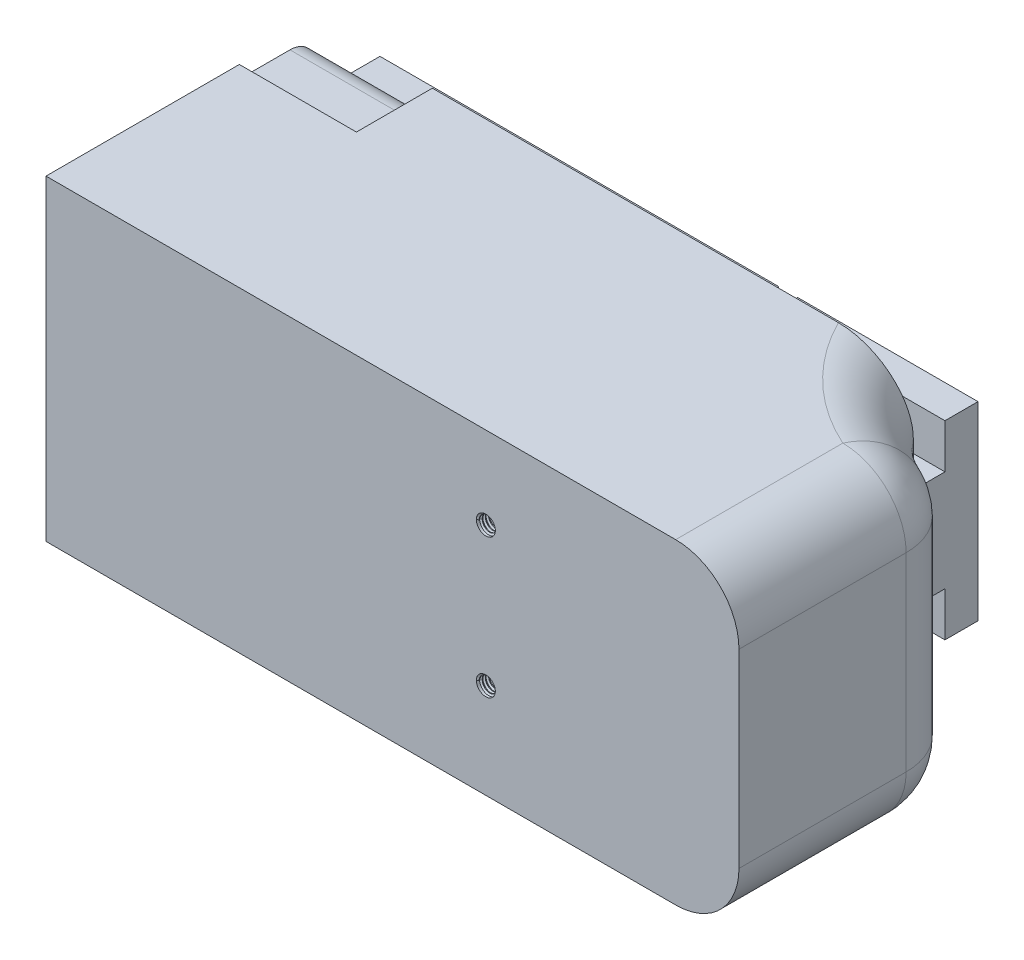
SolidWorks part; units mm, degrees
ref_plane "Front Plane" through (0, 0, 0) normal (0, 0, 1) x (1, 0, 0)
ref_plane "Top Plane" through (0, 0, 0) normal (0, 1, 0) x (1, 0, 0)
ref_plane "Right Plane" through (0, 0, 0) normal (1, 0, 0) x (0, 0, -1)
sketch "Sketch1" plane through (0, 0, 0) normal (0, 0, 1) x (1, 0, 0)
  line L0 (0, 0) -> (0, 50)
  line L1 (0, 50) -> (109.5, 50)
  line L2 (109.5, 50) -> (109.5, 0)
  line L3 (109.5, 0) -> (0, 0)
  dimension "D1" = 109.5
  dimension "D2" = 50
extrude "Boss-Extrude1" add sketch "Sketch1" along normal blind 52.55
sketch "Sketch2" plane through (0, 0, 0) normal (0, -1, 0) x (1, 0, 0)
  line L0 (0, 10) -> (109.5, 10)
  line L1 (0, 52.55) -> (0, 0) construction
  line L2 (109.5, 52.55) -> (109.5, 0) construction
  line L3 (0, 52.55) -> (109.5, 52.55) construction
  line L4 (0, 10) -> (0, 0)
  line L5 (0, 0) -> (109.5, 0)
  line L6 (109.5, 0) -> (109.5, 10)
  dimension "D1" = 42.55
extrude "Cut-Extrude1" cut sketch "Sketch2" against normal blind 10
sketch "Sketch3" plane through (0, 0, 0) normal (0, -1, 0) x (1, 0, 0)
  line L0 (0, 22) -> (18.5, 22)
  line L1 (0, 52.55) -> (0, 10) construction
  line L2 (18.5, 22) -> (18.5, 10)
  line L3 (109.5, 10) -> (0, 10) construction
  line L4 (0, 22) -> (0, 10)
  line L5 (0, 10) -> (18.5, 10)
  dimension "D1" = 18.5
  dimension "D2" = 12
extrude "Cut-Extrude2" cut sketch "Sketch3" against normal blind 2
fillet "Fillet1" radius 4 1 edges at (9.25, 2, 10)
sketch "Sketch4" plane through (0, 10, 0) normal (0, -1, 0) x (1, 0, 0)
  line L0 (18.5, 10) -> (18.5, 5)
  line L1 (109.5, 10) -> (0, 10) construction
  line L2 (18.5, 5) -> (109.5, 5)
  line L3 (109.5, 0) -> (109.5, 10) construction
  line L4 (109.5, 5) -> (109.5, 10)
  line L5 (109.5, 10) -> (18.5, 10)
  line L6 (0, 10) -> (0, 0) construction
  dimension "D1" = 18.5
  dimension "D2" = 5
extrude "Cut-Extrude3" cut sketch "Sketch4" against normal blind 7
sketch "Sketch5" plane through (0, 10, 0) normal (0, -1, 0) x (1, 0, 0)
  line L0 (94.5, 0) -> (94.5, 10)
  line L1 (0, 0) -> (109.5, 0) construction
  line L2 (109.5, 52.55) -> (109.5, 10) construction
  line L3 (94.5, 10) -> (117.8937, 10)
  line L4 (117.8937, 10) -> (117.8937, 0)
  line L5 (117.8937, 0) -> (94.5, 0)
  dimension "D1" = 10
  dimension "D2" = 15
extrude "Cut-Extrude4" cut sketch "Sketch5" against normal through all
sketch "Sketch6" plane through (0, 50, 0) normal (0, 1, 0) x (1, 0, 0)
  line L1 (94.5, -10) -> (0, -10)
  line L2 (0, -52.55) -> (0, 0) construction
  line L3 (0, -10) -> (0, 0)
  line L4 (0, 0) -> (94.5, 0)
  line L5 (94.5, 0) -> (94.5, -10)
extrude "Cut-Extrude5" cut sketch "Sketch6" against normal blind 10
sketch "Sketch8" plane through (0, 50, 0) normal (0, 1, 0) x (1, 0, 0)
  line L0 (0, -22) -> (18.5, -22)
  line L1 (0, -52.55) -> (0, -10) construction
  line L2 (18.5, -22) -> (18.5, -10)
  line L3 (109.5, -10) -> (0, -10) construction
  line L4 (18.5, -10) -> (0, -10)
  line L5 (0, -10) -> (0, -22)
  dimension "D1" = 18.5
  dimension "D2" = 12
extrude "Cut-Extrude6" cut sketch "Sketch8" against normal blind 2
fillet "Fillet2" radius 4 1 edges at (9.25, 48, 10)
sketch "Sketch9" plane through (0, 40, 0) normal (0, 1, 0) x (1, 0, 0)
  line L6 (18.5, -10) -> (18.5, -5)
  line L7 (0, -10) -> (94.5, -10) construction
  line L8 (18.5, -5) -> (94.5, -5)
  line L9 (94.5, -10) -> (94.5, 0) construction
  line L10 (94.5, -5) -> (94.5, -10)
  line L11 (94.5, -10) -> (18.5, -10)
  line L12 (0, 0) -> (0, -10) construction
  dimension "D1" = 18.5
  dimension "D2" = 5
extrude "Cut-Extrude7" cut sketch "Sketch9" against normal blind 7
sketch "Sketch10" plane through (0, 40, 0) normal (0, 1, 0) x (1, 0, 0)
  line L0 (94.5, 0) -> (0, 0) construction
  line L1 (109.5, -52.55) -> (109.5, -10) construction
  circle A0 centre (64.5, 0) radius 1.5
  dimension "D2" = 3
  dimension "D1" = 45
extrude "Cut-Extrude8" cut sketch "Sketch10" against normal through all
sketch "Sketch11" plane through (0, 0, 52.55) normal (0, 0, 1) x (1, 0, 0)
  line L0 (109.5, 0) -> (109.5, 50) construction
  line L1 (0, 0) -> (109.5, 0) construction
  circle A0 centre (69.5, 15) radius 1.5
  circle A1 centre (69.5, 37) radius 1.5
  dimension "D3" = 3
  dimension "D4" = 3
  dimension "D1" = 40
  dimension "D2" = 40
  dimension "D5" = 22
  dimension "D6" = 15
extrude "Cut-Extrude9" cut sketch "Sketch11" against normal blind 7.55
sketch "Sketch12" plane through (0, 50, 0) normal (0, 1, 0) x (1, 0, 0)
  line L0 (109.5, -10) -> (18.5, -10) construction
  line L1 (109.5, -52.55) -> (109.5, -10) construction
  line L2 (94.5, -10) -> (94.5, -5) construction
  line L3 (94.5, -10) -> (109.5, -10)
  line L4 (109.5, -10) -> (109.5, -18.85)
  line L5 (109.5, -52.55) -> (0, -52.55) construction
  arc A1 (109.5, -18.85) -> (94.5, -10) centre (113.9081, 5.7583) cw
  dimension "D1" = 25
  dimension "D2" = 0
  dimension "D3" = 33.7
extrude "Cut-Extrude10" cut sketch "Sketch12" against normal through all
fillet "Fillet3" radius 10 1 edges at (109.5, 25, 18.85)
sketch "Sketch13" plane through (0, 0, 0) normal (-1, 0, 0) x (0, 0, 1)
  line L0 (52.55, 50) -> (52.55, 0) construction
  line L1 (52.55, 50) -> (22, 50) construction
  line L2 (52.55, 0) -> (22, 0) construction
  circle A0 centre (37.552, 35) radius 3
  circle A1 centre (37.552, 15) radius 3
  dimension "D1" = 6
  dimension "D2" = 6
  dimension "D3" = 14.998
  dimension "D4" = 15
  dimension "D5" = 15
  dimension "D6" = 14.998
extrude "Cut-Extrude11" cut sketch "Sketch13" against normal blind 20
fillet "Fillet4" radius 10 3 edges at (98.6485, 50, 14.0443) (107.9014, 50, 20.7148) (109.5, 50, 39.3442)
fillet "Fillet5" radius 10 3 edges at (98.6485, 0, 14.0443) (107.9014, 0, 20.7148) (109.5, 0, 39.3442)
sketch "Sketch15" plane through (0, 0, 0) normal (0, 0, -1) x (-1, 0, 0)
  line L0 (0, 10) -> (0, 40)
  line L1 (0, 40) -> (-63, 40)
  line L2 (-63, 40) -> (-63, 10)
  line L3 (-63, 10) -> (0, 10)
  line L4 (-94.5, 10) -> (-66, 10)
  line L5 (-66, 10) -> (-66, 40)
  line L6 (-66, 40) -> (-94.5, 40)
  line L7 (-94.5, 40) -> (-94.5, 10)
extrude "Boss-Extrude2" add sketch "Sketch15" along normal blind 0.222
thread "Thread1" pitch 0.5 method extrude profile "Thread Profile1" start angle 0, offset 0, length 6, pitch 0.5, diameter 3
ref_plane "Plane1" through (68, 15, 52.55) normal (0, -1, 0) x (-1, 0, 0)
sketch "Thread Profile1" plane through (68, 15, 52.55) normal (0, -1, 0) x (-1, 0, 0)
  line L0 (0, 0) -> (0, 0.5) construction
  line L11 (0, 0) -> (0, 0.4375)
  line L12 (0, 0.4375) -> (-0.2706, 0.2812)
  line L13 (-0.2706, 0.2812) -> (-0.2706, 0.1562)
  line L15 (-0.2706, 0.1562) -> (0, 0)
  line L17 (-0.2706, 0.2187) -> (0, 0.2187) construction
  point P2 (0, 0)
  dimension "Pitch" = 0.5
  dimension "Profile_Angle" = 60
  dimension "Profile_Land" = 0.125
  dimension "Profile_Height" = 0.2706
thread "Thread2" pitch 0.5 method extrude profile "Thread Profile2" start angle 0, offset 0, length 6, pitch 0.5, diameter 3
ref_plane "Plane2" through (68, 37, 52.55) normal (0, -1, 0) x (-1, 0, 0)
sketch "Thread Profile2" plane through (68, 37, 52.55) normal (0, -1, 0) x (-1, 0, 0)
  line L0 (0, 0) -> (0, 0.5) construction
  line L11 (0, 0) -> (0, 0.4375)
  line L12 (0, 0.4375) -> (-0.2706, 0.2812)
  line L13 (-0.2706, 0.2812) -> (-0.2706, 0.1562)
  line L15 (-0.2706, 0.1562) -> (0, 0)
  line L17 (-0.2706, 0.2187) -> (0, 0.2187) construction
  point P2 (0, 0)
  dimension "Pitch" = 0.5
  dimension "Profile_Angle" = 60
  dimension "Profile_Land" = 0.125
  dimension "Profile_Height" = 0.2706
thread "Thread3" pitch 1 method extrude profile "Thread Profile3" start angle 0, offset 0, length 15, pitch 1, diameter 6
ref_plane "Plane3" through (0, 15, 34.552) normal (0, -1, 0) x (0, 0, -1)
sketch "Thread Profile3" plane through (0, 15, 34.552) normal (0, -1, 0) x (0, 0, -1)
  line L0 (0, 0) -> (0, 1) construction
  line L11 (0, 0) -> (0, 0.875)
  line L12 (0, 0.875) -> (-0.5413, 0.5625)
  line L13 (-0.5413, 0.5625) -> (-0.5413, 0.3125)
  line L15 (-0.5413, 0.3125) -> (0, 0)
  line L17 (-0.5413, 0.4375) -> (0, 0.4375) construction
  point P2 (0, 0)
  dimension "Pitch" = 1
  dimension "Profile_Angle" = 60
  dimension "Profile_Land" = 0.25
  dimension "Profile_Height" = 0.5413
thread "Thread4" pitch 1 method extrude profile "Thread Profile4" start angle 0, offset 0, length 15, pitch 1, diameter 6
ref_plane "Plane4" through (0, 35, 34.552) normal (0, -1, 0) x (0, 0, -1)
sketch "Thread Profile4" plane through (0, 35, 34.552) normal (0, -1, 0) x (0, 0, -1)
  line L0 (0, 0) -> (0, 1) construction
  line L11 (0, 0) -> (0, 0.875)
  line L12 (0, 0.875) -> (-0.5413, 0.5625)
  line L13 (-0.5413, 0.5625) -> (-0.5413, 0.3125)
  line L15 (-0.5413, 0.3125) -> (0, 0)
  line L17 (-0.5413, 0.4375) -> (0, 0.4375) construction
  point P2 (0, 0)
  dimension "Pitch" = 1
  dimension "Profile_Angle" = 60
  dimension "Profile_Land" = 0.25
  dimension "Profile_Height" = 0.5413
